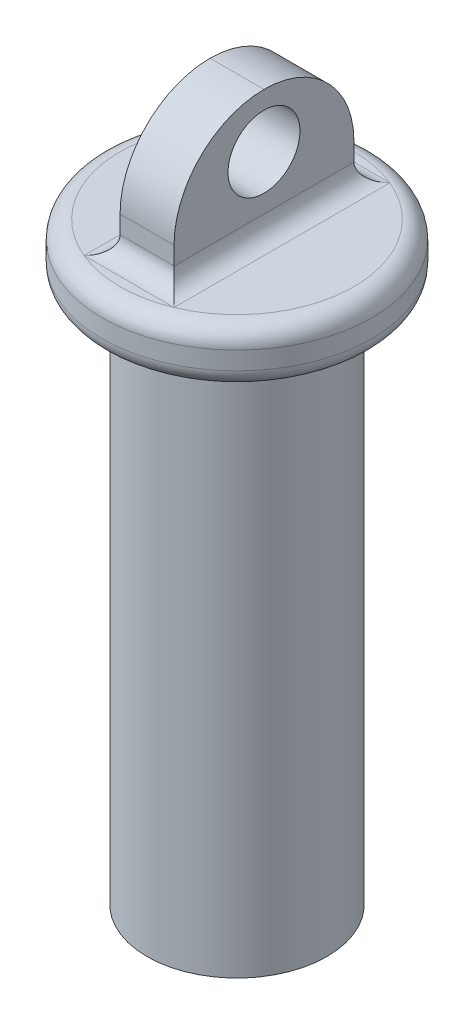
SolidWorks part; units mm, degrees
ref_plane "Front Plane" through (0, 0, 0) normal (0, 0, 1) x (1, 0, 0)
ref_plane "Top Plane" through (0, 0, 0) normal (0, 1, 0) x (1, 0, 0)
ref_plane "Right Plane" through (0, 0, 0) normal (1, 0, 0) x (0, 0, -1)
sketch "Sketch1" plane through (0, 0, 0) normal (0, 1, 0) x (1, 0, 0)
  circle A0 centre (0, 0) radius 5
  dimension "D1" = 10
extrude "Boss-Extrude1" add sketch "Sketch1" along normal blind 30
sketch "Sketch4" plane through (0, 30, 0) normal (0, 1, 0) x (1, 0, 0)
  circle A0 centre (0, 0) radius 7.5
  dimension "D1" = 15
extrude "Boss-Extrude3" add sketch "Sketch4" along normal blind 3
sketch "Sketch5" plane through (0, 33, 0) normal (0, 1, 0) x (1, 0, 0)
  line L1 (-1.5, 5) -> (1.5, 5)
  line L2 (-1.5, 5) -> (-1.5, -5)
  line L3 (-1.5, -5) -> (1.5, -5)
  line L4 (1.5, 5) -> (1.5, -5)
  line L5 (-1.5, 5) -> (1.5, -5) construction
  line L6 (-1.5, -5) -> (1.5, 5) construction
  point P0 (0, 0)
  dimension "D1" = 10
  dimension "D2" = 3
extrude "Boss-Extrude4" add sketch "Sketch5" along normal blind 7
sketch "Sketch6" plane through (1.5, 0, 0) normal (1, 0, 0) x (0, 0, -1)
  line L0 (-5, 40) -> (5, 40) construction
  circle A0 centre (0, 37) radius 2
  dimension "D1" = 4
  dimension "D2" = 3
extrude "Cut-Extrude2" cut sketch "Sketch6" against normal blind 7
fillet "Fillet1" radius 1 7 edges at (-1.5, 33, 0) (0, 33, 5) (1.5, 33, 0) (0, 33, -5) (0, 33, 7.5) (0, 30, 7.5) (0, 30, 5)
fillet "Fillet2" radius 5 2 edges at (0, 40, -5) (0, 40, 5)
